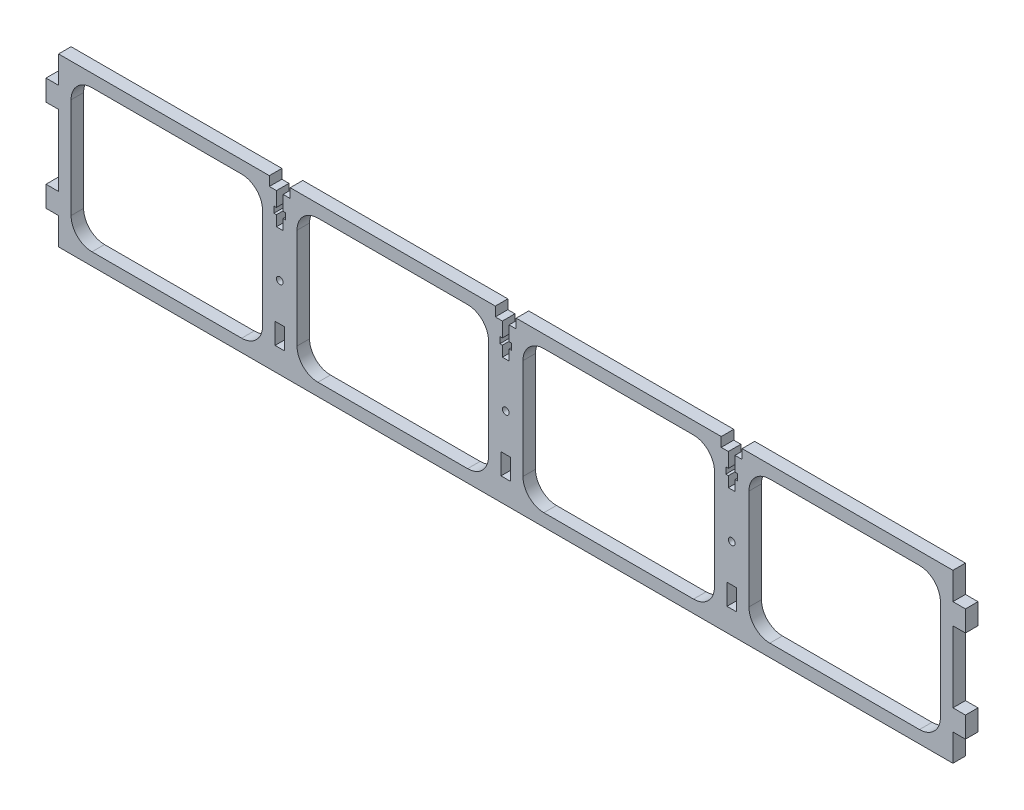
SolidWorks part; units mm, degrees
ref_plane "Front Plane" through (0, 0, 0) normal (0, 0, 1) x (1, 0, 0)
ref_plane "Top Plane" through (0, 0, 0) normal (0, 1, 0) x (1, 0, 0)
ref_plane "Right Plane" through (0, 0, 0) normal (1, 0, 0) x (0, 0, -1)
sketch "Sketch1" plane through (0, 0, 0) normal (0, 0, 1) x (1, 0, 0)
  line L1 (-214, -40) -> (214, -40)
  line L2 (-214, -40) -> (-214, 40)
  line L3 (-214, 40) -> (214, 40)
  line L4 (214, -40) -> (214, 40)
  line L5 (-214, -40) -> (214, 40) construction
  line L6 (-214, 40) -> (214, -40) construction
  point P0 (0, 0)
  dimension "D1" = 428
  dimension "D2" = 80
extrude "Boss-Extrude1" add sketch "Sketch1" along normal blind 6
sketch "Sketch2" plane through (0, 0, 6) normal (0, 0, 1) x (1, 0, 0)
  line L0 (-116.375, -42) -> (-116.375, -29) construction
  line L1 (-208, 40) -> (-208, -40) construction
  line L2 (-214, -34) -> (214, -34) construction
  line L3 (-214, -40) -> (214, -40) construction
  line L8 (214, -40) -> (214, 40)
  line L9 (214, 40) -> (-214, 40)
  line L10 (-214, 40) -> (-214, -40)
  line L11 (-214, -40) -> (214, -40)
  line L12 (214, -40) -> (214, 40) construction
  line L13 (214, 40) -> (-214, 40)
  line L14 (-214, 40) -> (-214, -40) construction
  line L15 (-208, -40) -> (214, -40) construction
  line L16 (-110.375, -42) -> (-110.375, -29) construction
  line L17 (-110.375, -42) -> (-110.375, -29) construction
  line L18 (-116.375, -24) -> (-116.375, 24)
  line L19 (-198, -34) -> (-126.375, -34)
  line L20 (-208, 24) -> (-208, -24)
  line L21 (-126.375, 34) -> (-198, 34)
  arc A0 (-198, 34) -> (-208, 24) centre (-198, 24) ccw
  arc A1 (-126.375, 34) -> (-116.375, 24) centre (-126.375, 24) cw
  arc A2 (-116.375, -24) -> (-126.375, -34) centre (-126.375, -24) cw
  arc A3 (-198, -34) -> (-208, -24) centre (-198, -24) cw
  dimension "D6" = 10
  dimension "D5" = 6
  dimension "D1" = 0
  dimension "D2" = 6
  dimension "D3" = 6
  dimension "D4" = 6
extrude "Cut-Extrude1" cut sketch "Sketch2" against normal up to next contours L18 L21 L20 L19 region at (-162.1875, 0, 6)
pattern_linear "LPattern1" count 4 spacing 108.125 along (1, 0, 0) of "Cut-Extrude1"
sketch "Sketch3" plane through (0, 0, 0) normal (0, 0, -1) x (-1, 0, 0)
  line L8 (-110.375, -29) -> (-110.375, -19) construction
  line L9 (-110.375, -19) -> (-105.875, -19) construction
  line L11 (-105.875, -29) -> (-110.375, -29) construction
  line L24 (-110.375, -29) -> (-110.375, -19)
  line L25 (-110.375, -19) -> (-105.875, -19)
  line L26 (-105.875, -19) -> (-105.875, -29)
  line L27 (-105.875, -29) -> (-110.375, -29)
  line L44 (-2.25, -29) -> (-2.25, -19) construction
  line L45 (-2.25, -19) -> (2.25, -19) construction
  line L46 (2.25, -19) -> (2.25, -29) construction
  line L47 (2.25, -29) -> (-2.25, -29) construction
  line L52 (-2.25, -29) -> (-2.25, -19)
  line L53 (-2.25, -19) -> (2.25, -19)
  line L54 (2.25, -19) -> (2.25, -29)
  line L55 (2.25, -29) -> (-2.25, -29)
  line L60 (105.875, -29) -> (105.875, -19) construction
  line L61 (105.875, -19) -> (110.375, -19) construction
  line L62 (110.375, -19) -> (110.375, -29) construction
  line L63 (110.375, -29) -> (105.875, -29) construction
  line L68 (105.875, -29) -> (105.875, -19)
  line L69 (105.875, -19) -> (110.375, -19)
  line L70 (110.375, -19) -> (110.375, -29)
  line L71 (110.375, -29) -> (105.875, -29)
  circle A3 centre (108.125, -1) radius 1.6 construction
  circle A4 centre (0, -1) radius 1.6 construction
  circle A5 centre (-108.125, -1) radius 1.6 construction
  circle A6 centre (108.125, -1) radius 1.6
  circle A7 centre (0, -1) radius 1.6
  circle A8 centre (-108.125, -1) radius 1.6
extrude "Cut-Extrude2" cut sketch "Sketch3" against normal through all
sketch "Sketch4" plane through (0, 0, 0) normal (0, 0, -1) x (-1, 0, 0)
  line L0 (-111.5, 17) -> (-214, 17) construction
  line L1 (-214, -40) -> (-214, 40) construction
  line L2 (-108.5, 0) -> (-214, 0) construction
  line L3 (-220, 21.3321) -> (-220, 40) construction
  line L4 (-214, 17) -> (-220, 17)
  line L5 (-214, 17) -> (-214, 27)
  line L6 (-214, 27) -> (-220, 27)
  line L7 (-220, 17) -> (-220, 27)
  line L9 (-220, -17) -> (-220, -27)
  line L10 (-214, -27) -> (-220, -27)
  line L11 (-214, -17) -> (-214, -27)
  line L12 (-214, -17) -> (-220, -17)
  line L13 (0, 0) -> (0, 40) construction
  line L14 (-214, 40) -> (214, 40) construction
  line L15 (214, -17) -> (220, -17)
  line L16 (214, -17) -> (214, -27)
  line L17 (214, -27) -> (220, -27)
  line L18 (220, -17) -> (220, -27)
  line L19 (220, 17) -> (220, 27)
  line L20 (214, 27) -> (220, 27)
  line L21 (214, 17) -> (214, 27)
  line L22 (214, 17) -> (220, 17)
  point P13 (-108.5, -1)
  dimension "D1" = 34
  dimension "D2" = 10
extrude "Boss-Extrude2" add sketch "Sketch4" against normal blind 6
sketch "Sketch5" plane through (0, 40, 0) normal (0, 1, 0) x (1, 0, 0)
  line L0 (214, -6) -> (-214, -6) construction
  line L1 (-113.125, 0) -> (-103.125, 0)
  line L2 (-113.125, 0) -> (-113.125, -6)
  line L3 (-113.125, -6) -> (-103.125, -6)
  line L4 (-103.125, 0) -> (-103.125, -6)
  line L5 (-113.125, 0) -> (-103.125, -6) construction
  line L6 (-113.125, -6) -> (-103.125, 0) construction
  line L7 (-103.125, -6) -> (-103.125, 0) construction
  line L8 (5, -6) -> (5, 0) construction
  line L9 (-5, 0) -> (5, 0)
  line L10 (-5, 0) -> (-5, -6)
  line L11 (-5, -6) -> (5, -6)
  line L12 (5, 0) -> (5, -6)
  line L13 (-5, 0) -> (5, -6) construction
  line L14 (-5, -6) -> (5, 0) construction
  line L15 (113.125, -6) -> (113.125, 0) construction
  line L16 (103.125, 0) -> (113.125, 0)
  line L17 (103.125, 0) -> (103.125, -6)
  line L18 (103.125, -6) -> (113.125, -6)
  line L19 (113.125, 0) -> (113.125, -6)
  line L20 (103.125, 0) -> (113.125, -6) construction
  line L21 (103.125, -6) -> (113.125, 0) construction
  point P0 (-108.125, -3)
  point P10 (0, -3)
  point P18 (108.125, -3)
extrude "Cut-Extrude3" cut sketch "Sketch5" against normal blind 4.5
sketch "Sketch6" plane through (0, 0, 0) normal (0, 0, -1) x (-1, 0, 0)
  line L12 (-109.725, 35.5) -> (-109.725, 28.5)
  line L13 (-106.525, 35.5) -> (-109.725, 35.5)
  line L14 (-106.525, 28.5) -> (-106.525, 35.5)
  line L15 (-105.325, 28.5) -> (-106.525, 28.5)
  line L16 (-105.325, 25.5) -> (-105.325, 28.5)
  line L17 (-106.525, 25.5) -> (-105.325, 25.5)
  line L18 (-106.525, 20.5) -> (-106.525, 25.5)
  line L19 (-109.725, 20.5) -> (-106.525, 20.5)
  line L20 (-109.725, 25.5) -> (-109.725, 20.5)
  line L21 (-110.925, 25.5) -> (-109.725, 25.5)
  line L22 (-110.925, 28.5) -> (-110.925, 25.5)
  line L23 (-109.725, 28.5) -> (-110.925, 28.5)
  line L24 (-109.725, 35.5) -> (-109.725, 28.5)
  line L25 (-106.525, 35.5) -> (-109.725, 35.5)
  line L26 (-106.525, 28.5) -> (-106.525, 35.5)
  line L27 (-105.325, 28.5) -> (-106.525, 28.5)
  line L28 (-105.325, 25.5) -> (-105.325, 28.5)
  line L29 (-106.525, 25.5) -> (-105.325, 25.5)
  line L30 (-106.525, 20.5) -> (-106.525, 25.5)
  line L31 (-109.725, 20.5) -> (-106.525, 20.5)
  line L32 (-109.725, 25.5) -> (-109.725, 20.5)
  line L33 (-110.925, 25.5) -> (-109.725, 25.5)
  line L34 (-110.925, 28.5) -> (-110.925, 25.5)
  line L35 (-109.725, 28.5) -> (-110.925, 28.5)
  line L36 (-1.595, 28.5) -> (-2.795, 28.5)
  line L37 (-2.795, 28.5) -> (-2.795, 25.5)
  line L38 (-2.795, 25.5) -> (-1.595, 25.5)
  line L39 (-1.595, 25.5) -> (-1.595, 20.5)
  line L40 (-1.595, 20.5) -> (1.605, 20.5)
  line L41 (1.605, 20.5) -> (1.605, 25.5)
  line L42 (1.605, 25.5) -> (2.805, 25.5)
  line L43 (2.805, 25.5) -> (2.805, 28.5)
  line L44 (2.805, 28.5) -> (1.605, 28.5)
  line L45 (1.605, 28.5) -> (1.605, 35.5)
  line L46 (1.605, 35.5) -> (-1.595, 35.5)
  line L47 (-1.595, 35.5) -> (-1.595, 28.5)
  line L48 (-1.595, 28.5) -> (-2.795, 28.5)
  line L49 (-2.795, 28.5) -> (-2.795, 25.5)
  line L50 (-2.795, 25.5) -> (-1.595, 25.5)
  line L51 (-1.595, 25.5) -> (-1.595, 20.5)
  line L52 (-1.595, 20.5) -> (1.605, 20.5)
  line L53 (1.605, 20.5) -> (1.605, 25.5)
  line L54 (1.605, 25.5) -> (2.805, 25.5)
  line L55 (2.805, 25.5) -> (2.805, 28.5)
  line L56 (2.805, 28.5) -> (1.605, 28.5)
  line L57 (1.605, 28.5) -> (1.605, 35.5)
  line L58 (1.605, 35.5) -> (-1.595, 35.5)
  line L59 (-1.595, 35.5) -> (-1.595, 28.5)
  line L60 (106.535, 35.5) -> (106.535, 28.5)
  line L61 (109.735, 35.5) -> (106.535, 35.5)
  line L62 (109.735, 28.5) -> (109.735, 35.5)
  line L63 (110.935, 28.5) -> (109.735, 28.5)
  line L64 (110.935, 25.5) -> (110.935, 28.5)
  line L65 (109.735, 25.5) -> (110.935, 25.5)
  line L66 (109.735, 20.5) -> (109.735, 25.5)
  line L67 (106.535, 20.5) -> (109.735, 20.5)
  line L68 (106.535, 25.5) -> (106.535, 20.5)
  line L69 (105.335, 25.5) -> (106.535, 25.5)
  line L70 (105.335, 28.5) -> (105.335, 25.5)
  line L71 (106.535, 28.5) -> (105.335, 28.5)
  line L72 (106.535, 35.5) -> (106.535, 28.5)
  line L73 (109.735, 35.5) -> (106.535, 35.5)
  line L74 (109.735, 28.5) -> (109.735, 35.5)
  line L75 (110.935, 28.5) -> (109.735, 28.5)
  line L76 (110.935, 25.5) -> (110.935, 28.5)
  line L77 (109.735, 25.5) -> (110.935, 25.5)
  line L78 (109.735, 20.5) -> (109.735, 25.5)
  line L79 (106.535, 20.5) -> (109.735, 20.5)
  line L80 (106.535, 25.5) -> (106.535, 20.5)
  line L81 (105.335, 25.5) -> (106.535, 25.5)
  line L82 (105.335, 28.5) -> (105.335, 25.5)
  line L83 (106.535, 28.5) -> (105.335, 28.5)
  dimension "D1" = 0
  dimension "D2" = 0
  dimension "D3" = 0
extrude "Cut-Extrude4" cut sketch "Sketch6" against normal up to next
